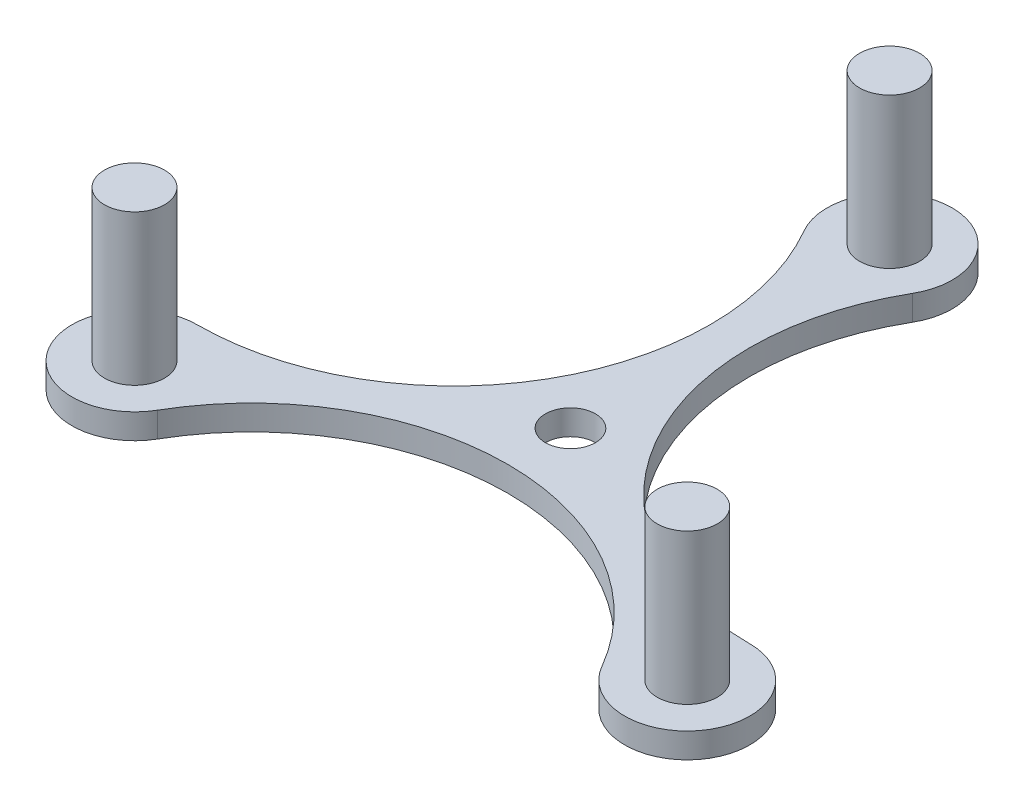
SolidWorks part; units mm, degrees
ref_plane "Front Plane" through (0, 0, 0) normal (0, 0, 1) x (1, 0, 0)
ref_plane "Top Plane" through (0, 0, 0) normal (0, 1, 0) x (1, 0, 0)
ref_plane "Right Plane" through (0, 0, 0) normal (1, 0, 0) x (0, 0, -1)
sketch "Sketch1" plane through (0, 0, 0) normal (0, 1, 0) x (1, 0, 0)
  line L0 (0, 25.5) -> (0, 0) construction
  line L1 (0, 0) -> (22.0836, -12.75) construction
  line L2 (-22.0836, -12.75) -> (0, 0) construction
  arc A0 (-22.0836, -12.75) -> (-20.7872, -14.7697) centre (0, 0) ccw construction
  circle A1 centre (0, 25.5) radius 2.4
  circle A2 centre (22.0836, -12.75) radius 2.4
  circle A3 centre (-22.0836, -12.75) radius 2.4
  arc A4 (0, -5) -> (4.3301, -2.5) centre (0, 0) ccw construction
  arc A5 (4.3301, 23) -> (-4.3301, 23) centre (0, 25.5) ccw
  arc A6 (17.7535, -15.25) -> (22.0836, -7.75) centre (22.0836, -12.75) ccw
  arc A7 (-22.0836, -7.75) -> (-17.7535, -15.25) centre (-22.0836, -12.75) ccw
  circle A8 centre (-22.0836, 12.75) radius 20.5
  circle A9 centre (22.0836, 12.75) radius 20.5
  circle A10 centre (0, -25.5) radius 20.5
  circle A11 centre (0, 0) radius 2
  arc A12 (-24.1471, -8.1956) -> (-23.1845, -10.6174) centre (0, 0) ccw construction
  arc A13 (-19.1712, -16.8142) -> (19.1712, -16.8142) centre (0, 0) ccw
  arc A14 (-20.7872, -14.7697) -> (-19.1712, -16.8142) centre (0, 0) ccw construction
  arc A15 (24.1471, -8.1956) -> (4.9759, 25.0098) centre (0, 0) ccw
  arc A16 (19.1712, -16.8142) -> (20.7872, -14.7697) centre (0, 0) ccw construction
  arc A17 (20.7872, -14.7697) -> (22.0836, -12.75) centre (0, 0) ccw construction
  arc A18 (22.0836, -12.75) -> (23.1845, -10.6174) centre (0, 0) ccw construction
  arc A19 (23.1845, -10.6174) -> (24.1471, -8.1956) centre (0, 0) ccw construction
  arc A20 (-23.1845, -10.6174) -> (-22.0836, -12.75) centre (0, 0) ccw construction
  arc A21 (-4.9759, 25.0098) -> (-24.1471, -8.1956) centre (0, 0) ccw
  arc A22 (-2.3973, 25.3871) -> (-4.9759, 25.0098) centre (0, 0) ccw construction
  arc A23 (0, 25.5) -> (-2.3973, 25.3871) centre (0, 0) ccw construction
  arc A24 (2.3973, 25.3871) -> (0, 25.5) centre (0, 0) ccw construction
  arc A25 (4.9759, 25.0098) -> (2.3973, 25.3871) centre (0, 0) ccw construction
  arc A26 (0, 20.5) -> (4.3301, 23) centre (0, 25.5) ccw construction
  arc A27 (-4.3301, 23) -> (0, 20.5) centre (0, 25.5) ccw construction
  arc A28 (22.0836, -7.75) -> (17.7535, -10.25) centre (22.0836, -12.75) ccw construction
  arc A29 (17.7535, -10.25) -> (17.7535, -15.25) centre (22.0836, -12.75) ccw construction
  arc A30 (-17.7535, -10.25) -> (-22.0836, -7.75) centre (-22.0836, -12.75) ccw construction
  arc A31 (-17.7535, -15.25) -> (-17.7535, -10.25) centre (-22.0836, -12.75) ccw construction
  arc A32 (-4.3301, -2.5) -> (0, -5) centre (0, 0) ccw construction
  arc A33 (-4.3301, 2.5) -> (-4.3301, -2.5) centre (0, 0) ccw construction
  arc A34 (0, 5) -> (-4.3301, 2.5) centre (0, 0) ccw construction
  arc A35 (4.3301, 2.5) -> (0, 5) centre (0, 0) ccw construction
  arc A36 (4.3301, -2.5) -> (4.3301, 2.5) centre (0, 0) ccw construction
  dimension "D1" = 51
  dimension "D3" = 4.8
  dimension "D4" = 10
  dimension "D5" = 10
  dimension "D6" = 4
  dimension "D2" = 120
extrude "Boss-Extrude1" add sketch "Sketch1" along normal blind 2 contours A10 A6 A9 A5 A8 A7 A11 A1 A2 A3 | A3 | A2 | A1 region at (0, 0, -25.5) region at (22.0836, 0, 12.75) region at (-22.0836, 0, 12.75) region at (3.7019, 0, -2.1373)
extrude "Boss-Extrude2" add sketch "Sketch1<3>" along normal blind 12 from surface contours A3 | A2 | A1 region at (0, 0, -25.5) region at (22.0836, 0, 12.75) region at (-22.0836, 0, 12.75) starting at face at (0, 2, 2)
sketch "Sketch1<3>" plane through (0, 0, 0) normal (0, 1, 0) x (1, 0, 0) same geometry as "Sketch1"
